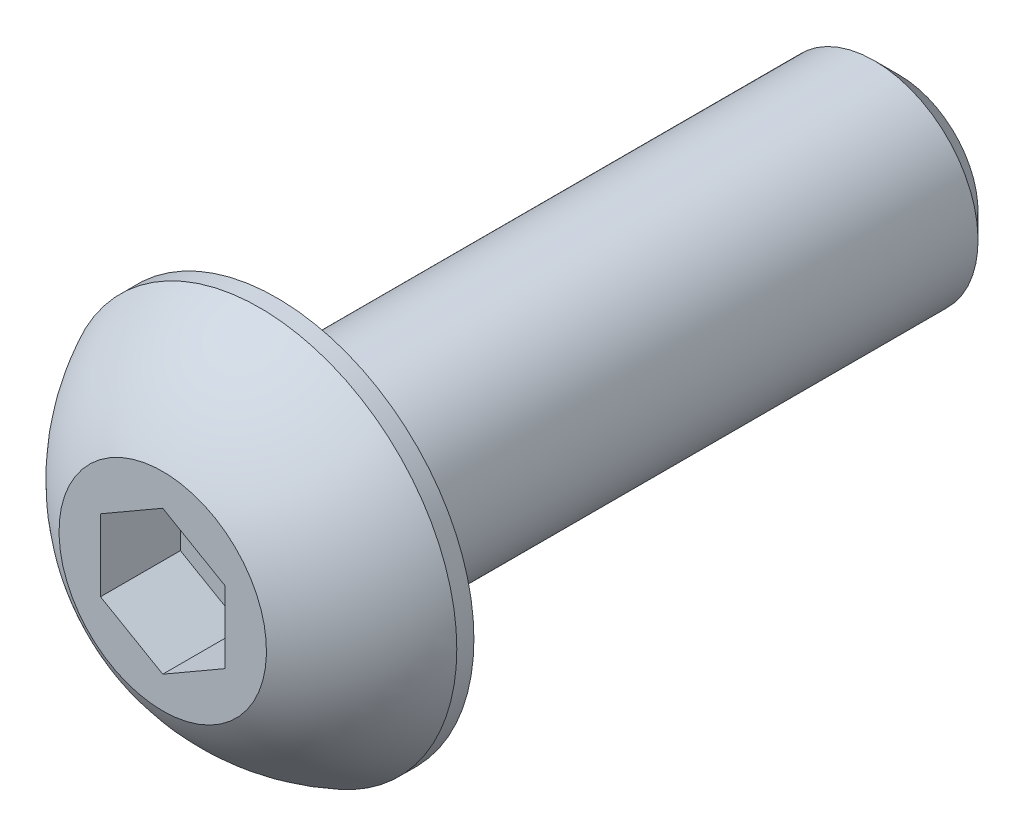
SolidWorks part; units mm, degrees
ref_plane "Front" through (0, 0, 0) normal (0, 0, 1) x (1, 0, 0)
ref_plane "Top" through (0, 0, 0) normal (0, 1, 0) x (1, 0, 0)
ref_plane "Right" through (0, 0, 0) normal (1, 0, 0) x (0, 0, -1)
sketch "Sketch1" plane through (0, 0, 0) normal (1, 0, 0) x (0, 0, -1)
  line L2 (2.75, 2.5) -> (17.75, 2.5)
  line L3 (17.75, 2.5) -> (17.75, 0)
  line L4 (17.75, 0) -> (2.75, 0)
  line L6 (2.3375, 4.75) -> (2.75, 4.75) construction
  line L7 (17.75, 2.5) -> (17.75, -2.5) construction
  line L8 (0, 0) -> (2.75, 0) construction
  line L9 (2.75, 4.75) -> (2.75, -4.75) construction
  line L11 (2.75, 2.5) -> (2.75, 0)
  line L13 (0, 1.5) -> (0, -1.5) construction
  line L14 (0, 1.5) -> (0, 2.5) construction
  arc A3 (0, 2.5) -> (2.3375, 4.75) centre (4.6581, 0) cw construction
  dimension "D1" = 0.4125
revolve "Revolve1" add sketch "Sketch1" angle 360 mid plane about L4
sketch "Sketch3" plane through (0, 0, -17.75) normal (0, 0, -1) x (-1, 0, 0)
  circle A0 centre (0, 0) radius 2.5
curve "Helix/Spiral1" [suppressed] pitch 0.8 height 15.8 turns 19.75
sketch "Sketch2" plane through (0, 0, 0) normal (1, 0, 0) x (0, 0, -1)
  line L0 (17.75, 2.5) -> (18.45, 2.5)
  line L1 (18.45, 2.5) -> (18.15, 1.9804)
  line L2 (18.15, 1.9804) -> (18.05, 1.9804)
  line L3 (18.05, 1.9804) -> (17.75, 2.5)
  line L4 (17.9, 2.2402) -> (18.3, 2.2402) construction
  dimension "D1" = 60
  dimension "D2" = 0.1
  dimension "D3" = 0.4
chamfer "Chamfer1" distance 0.6 angle 45 1 edges at (0, 2.5, -17.75)
sweep "Cut-Sweep1" [suppressed] cut profiles "Sketch2" path "Helix/Spiral1"
sketch "Sketch7" plane through (0, 0, 0) normal (1, 0, 0) x (0, 0, -1)
  line L6 (2.3375, 4.75) -> (2.75, 4.75) construction
  line L8 (0, 0) -> (2.75, 0) construction
  line L11 (2.75, 4.75) -> (2.75, -4.75) construction
  line L12 (2.3375, 4.75) -> (2.75, 4.75)
  line L13 (0, 0) -> (2.75, 0)
  line L14 (0, 1.5) -> (0, -1.5) construction
  line L15 (2.75, 4.75) -> (2.75, 0)
  line L16 (0, 2.5) -> (0, 0)
  arc A2 (2.3375, 4.75) -> (0, 2.5) centre (4.6581, 0) ccw construction
  arc A3 (2.3375, 4.75) -> (0, 2.5) centre (4.6581, 0) ccw
revolve "Revolve2" add sketch "Sketch7" angle 360 mid plane about L13
sketch "Sketch5" plane through (0, 0, 0) normal (0, 0, 1) x (1, 0, 0)
  line L1 (1.5, -0.866) -> (1.5, 0.866)
  line L2 (1.5, 0.866) -> (0, 1.7321)
  line L3 (0, 1.7321) -> (-1.5, 0.866)
  line L4 (-1.5, 0.866) -> (-1.5, -0.866)
  line L5 (-1.5, -0.866) -> (0, -1.7321)
  line L6 (0, -1.7321) -> (1.5, -0.866)
  circle A0 centre (0, 0) radius 1.5 construction
extrude "Cut-Extrude2" cut sketch "Sketch5" against normal blind 1.925
sketch "Sketch6" plane through (0, 0, 0) normal (0, 0, 1) x (1, 0, 0)
  circle A0 centre (0, 0) radius 1.7321
extrude "Cut-Extrude3" [suppressed] cut sketch "Sketch6" against normal blind 1.925 draft 45
sketch "Sketch9" [suppressed] plane through (0, 0, -6.6) normal (0, 0, 1) x (1, 0, 0)
  circle A2 centre (0, 0) radius 6
extrude "Boss-Extrude2" [suppressed] add sketch "Sketch9" against normal offset from surface (19 mm away) 32
sketch "Sketch10" plane through (0, 0, 0) normal (1, 0, 0) x (0, 0, -1)
  line L0 (17.75, 2.5) -> (17.75, -2.5) construction
  point P0 (16.55, -2.5)
  dimension "D1" = 1.2
equation "\"D3@Helix/Spiral1\" = \"Lg@Sketch1\" + \"D4@Helix/Spiral1\""
equation "\"D2@Sketch2\" = \"D4@Helix/Spiral1\" * .125"
equation "\"D3@Sketch2\" = \"D4@Helix/Spiral1\" * .5"
equation "\"D1@Chamfer1\" = \"D4@Helix/Spiral1\" * .75"
equation "\"D1@Cut-Extrude2\" = \"Head Ht@Sketch1\" * .7"
equation "\"D1@Sketch1\" = \"Head Ht@Sketch1\" * .15"
equation "\"D1@Sketch10\" = \"D4@Helix/Spiral1\" * 1.5"
equation "\"D1@Cut-Extrude3\" = \"D1@Cut-Extrude2\""
